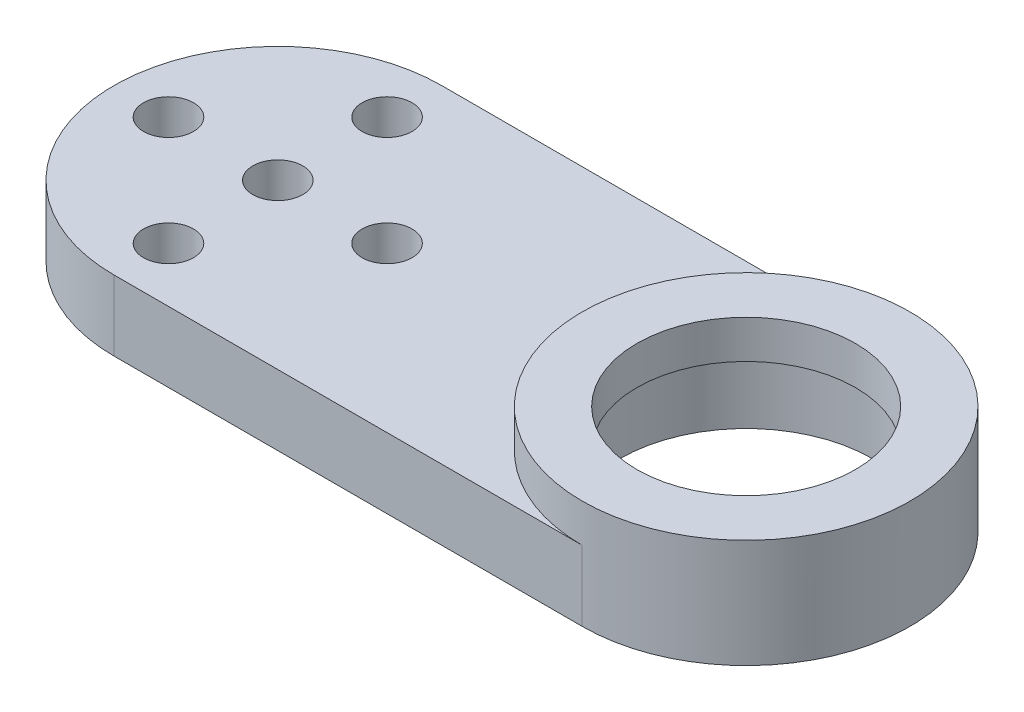
SolidWorks part; units mm, degrees
ref_plane "Front Plane" through (0, 0, 0) normal (0, 0, 1) x (1, 0, 0)
ref_plane "Top Plane" through (0, 0, 0) normal (0, 1, 0) x (1, 0, 0)
ref_plane "Right Plane" through (0, 0, 0) normal (1, 0, 0) x (0, 0, -1)
sketch "Sketch2" plane through (0, 0, 0) normal (0, 1, 0) x (1, 0, 0)
  line L0 (15, 0) -> (-15, 0) construction
  line L1 (15, 10.5) -> (-15, 10.5)
  line L2 (15, -10.5) -> (-15, -10.5)
  arc A0 (15, 10.5) -> (15, -10.5) centre (15, 0) cw
  arc A1 (-15, 10.5) -> (-15, -10.5) centre (-15, 0) ccw
  point P4 (0, 0)
  dimension "D1" = 30
  dimension "D2" = 10.5
  dimension "D3" = 10.5
extrude "Boss-Extrude1" add sketch "Sketch2" along normal blind 4.5
sketch "Sketch4" plane through (0, 4.5, 0) normal (0, 1, 0) x (1, 0, 0)
  line L0 (-15, 0) -> (-8, 0) construction
  line L1 (15, 0) -> (-15, 0) construction
  line L2 (-15, 0) -> (-8, 0) construction
  circle A0 centre (-15, 0) radius 1.6
  circle A1 centre (-8, 0) radius 1.6
  circle A2 centre (-15, -7) radius 1.6
  circle A3 centre (-22, 0) radius 1.6
  circle A4 centre (-15, 7) radius 1.6
  dimension "D1" = 3.2
  dimension "D2" = 7
  dimension "D3" = 4
extrude "Servo horn holes" cut sketch "Sketch4" against normal through all
sketch "Sketch5" plane through (0, 0, 0) normal (0, -1, 0) x (-1, 0, 0)
  circle A0 centre (-15, 0) radius 8.1
  dimension "D1" = 16.2
extrude "Bearing press fit" cut sketch "Sketch5" against normal through all
sketch "Sketch6" plane through (0, 4.5, 0) normal (0, 1, 0) x (1, 0, 0)
  circle A0 centre (15, 0) radius 10.5
  circle A1 centre (15, 0) radius 7
  dimension "D1" = 14
extrude "Boss-Extrude2" add sketch "Sketch6" along normal blind 2.45
